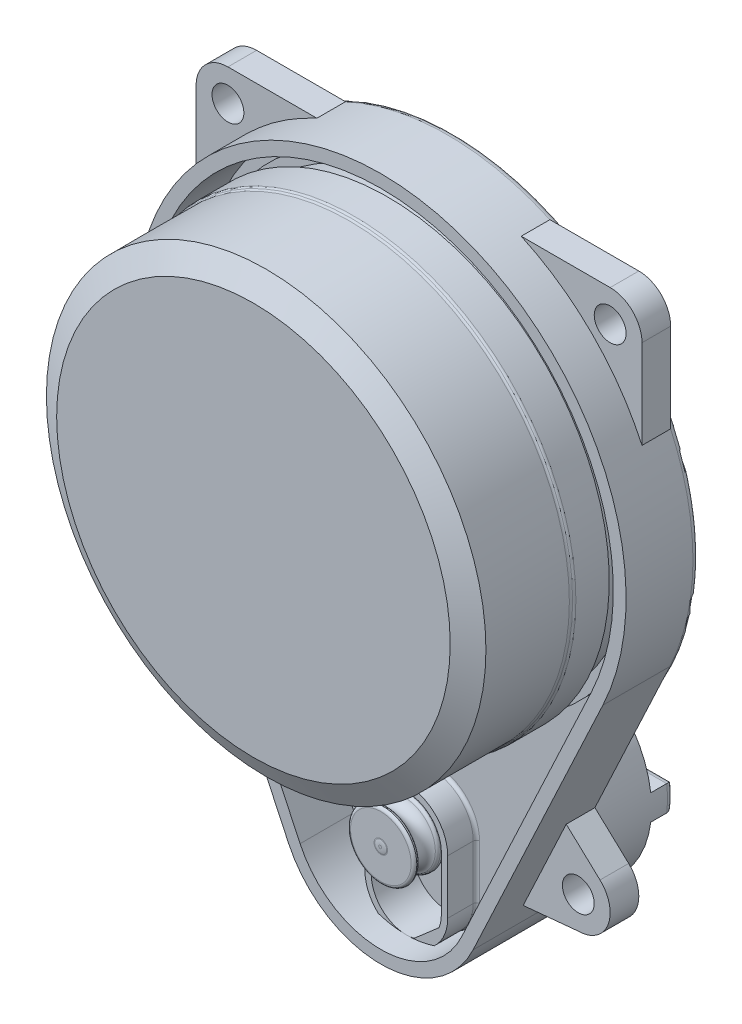
SolidWorks part; units mm, degrees
ref_plane "Front Plane" through (0, 0, 0) normal (0, 0, 1) x (1, 0, 0)
ref_plane "Top Plane" through (0, 0, 0) normal (0, 1, 0) x (1, 0, 0)
ref_plane "Right Plane" through (0, 0, 0) normal (1, 0, 0) x (0, 0, -1)
sketch "Sketch1" plane through (0, 0, 0) normal (0, 0, 1) x (1, 0, 0)
  circle A0 centre (0, 0) radius 34.5
  dimension "D1" = 69
extrude "Boss-Extrude1" add sketch "Sketch1" along normal blind 20
sketch "Sketch3" plane through (0, 0, 0) normal (0, 0, -1) x (-1, 0, 0)
  line L0 (0, 0) -> (0, -53) construction
  line L1 (-14.4866, -59.7925) -> (-34.8585, -16.3443)
  line L2 (14.4866, -59.7925) -> (34.8585, -16.3443)
  line L3 (12.6758, -58.9434) -> (33.0476, -15.4953)
  line L4 (-12.6758, -58.9434) -> (-33.0476, -15.4953)
  arc A2 (34.8585, -16.3443) -> (-34.8585, -16.3443) centre (0, 0) ccw
  circle A3 centre (0, 0) radius 36.5
  circle A4 centre (0, 0) radius 36.5
  arc A6 (-12.6758, -58.9434) -> (12.6758, -58.9434) centre (0, -53) ccw
  circle A7 centre (0, 0) radius 38.5 construction
  arc A8 (-14.4866, -59.7925) -> (14.4866, -59.7925) centre (0, -53) ccw
  point P2 (38.5, 0)
  point P9 (15.3009, -48.3221)
  point P20 (14, -53)
  dimension "D3" = 53
  dimension "D1" = 2
  dimension "D2" = 2
  dimension "D6" = 2
  dimension "D7" = 2
extrude "Boss-Extrude2" add sketch "Sketch3" along normal blind 10.5 separate body contours L1 A8 L2 A2 A6 L4 A4 L3
sketch "Sketch4" plane through (0, 0, 0) normal (0, 0, -1) x (-1, 0, 0)
  circle A2 centre (0, 0) radius 34.5
  circle A3 centre (0, 0) radius 34.5
  dimension "D1" = 0
extrude "Boss-Extrude3" add sketch "Sketch4" along normal blind 10.5
sketch "Sketch5" plane through (0, 0, -10.5) normal (0, 0, -1) x (-1, 0, 0)
  line L4 (-34.8585, -16.3443) -> (-14.4866, -59.7925)
  line L5 (14.4866, -59.7925) -> (34.8585, -16.3443)
  line L6 (-34.8585, -16.3443) -> (-14.4866, -59.7925)
  line L7 (14.4866, -59.7925) -> (34.8585, -16.3443)
  arc A4 (-14.4866, -59.7925) -> (14.4866, -59.7925) centre (0, -53) ccw
  arc A5 (34.8585, -16.3443) -> (-34.8585, -16.3443) centre (0, 0) ccw
  arc A6 (-14.4866, -59.7925) -> (14.4866, -59.7925) centre (0, -53) ccw
  arc A7 (34.8585, -16.3443) -> (-34.8585, -16.3443) centre (0, 0) ccw
  dimension "D1" = 0
extrude "Boss-Extrude4" add sketch "Sketch5" against normal blind 2
sketch "Sketch6" plane through (0, 0, -8.5) normal (0, 0, 1) x (1, 0, 0)
  line L0 (0, -53) -> (0, -61.5) construction
  line L1 (5.5, -53) -> (5.5, -61.5)
  line L2 (-5.5, -53) -> (-5.5, -61.5)
  arc A0 (5.5, -53) -> (-5.5, -53) centre (0, -53) ccw
  arc A1 (-5.5, -61.5) -> (5.5, -61.5) centre (0, -61.5) ccw
  arc A2 (-12.6758, -58.9434) -> (12.6758, -58.9434) centre (0, -53) ccw construction
  point P2 (0, -57.25)
  point P9 (0, -67)
  dimension "D1" = 11
extrude "Cut-Extrude1" cut sketch "Sketch6" against normal blind 2.5
sketch "Sketch7" plane through (0, 0, -10.5) normal (0, 0, -1) x (-1, 0, 0)
  circle A0 centre (0, -53) radius 16
extrude "Boss-Extrude5" add sketch "Sketch7" along normal blind 23
sketch "Sketch8" plane through (0, 0, -33.5) normal (0, 0, -1) x (-1, 0, 0)
  circle A0 centre (0, -53) radius 3.75
  circle A1 centre (0, -53) radius 16
  dimension "D1" = 7.5
extrude "Cut-Extrude2" cut sketch "Sketch8" against normal blind 3.5
sketch "Sketch9" plane through (0, 0, -30) normal (0, 0, -1) x (-1, 0, 0)
  line L0 (3.75, -53) -> (16, -53) construction
  line L1 (0, -49.25) -> (0, -37) construction
  line L2 (2, -49.8279) -> (2, -37.1255)
  line L3 (3.1721, -51) -> (15.8745, -51)
  line L4 (3.75, -51) -> (16, -51) construction
  line L5 (2, -49.25) -> (2, -37) construction
  line L6 (2, -56.1721) -> (2, -68.8745)
  line L7 (3.1721, -55) -> (15.8745, -55)
  line L8 (-3.1721, -55) -> (-15.8745, -55)
  line L9 (-2, -56.1721) -> (-2, -68.8745)
  line L10 (-2, -49.8279) -> (-2, -37.1255)
  line L11 (-3.1721, -51) -> (-15.8745, -51)
  circle A0 centre (0, -53) radius 3.75 construction
  arc A1 (14.4866, -59.7925) -> (-14.4866, -59.7925) centre (0, -53) ccw construction
  circle A2 centre (0, -53) radius 3.75 construction
  circle A3 centre (0, -53) radius 16 construction
  arc A4 (3.1721, -51) -> (2, -49.8279) centre (0, -53) ccw
  arc A5 (2, -56.1721) -> (3.1721, -55) centre (0, -53) ccw
  circle A6 centre (0, -53) radius 16
  arc A7 (15.8745, -51) -> (2, -37.1255) centre (0, -53) ccw
  arc A8 (2, -68.8745) -> (15.8745, -55) centre (0, -53) ccw
  arc A9 (-2, -49.8279) -> (-3.1721, -51) centre (0, -53) ccw
  arc A11 (-15.8745, -55) -> (-2, -68.8745) centre (0, -53) ccw
  arc A12 (-2, -37.1255) -> (-15.8745, -51) centre (0, -53) ccw
  arc A13 (-3.1721, -55) -> (-2, -56.1721) centre (0, -53) ccw
  point P28 (0, -53)
  point P36 (0, -53)
  point P43 (0, -53)
  point P50 (0, -53)
  point P51 (0, -53)
  dimension "D1" = 2
  dimension "D2" = 2
  dimension "D3" = 0
  dimension "D5" = 4
extrude "Cut-Extrude3" cut sketch "Sketch9" against normal blind 3.5
fillet "Fillet1" radius 1 24 edges at (-2, -49.8279, -28.25) (2, -49.8279, -28.25) (2, -56.1721, -28.25) (-2, -56.1721, -28.25) (-3.1721, -55, -28.25) (-3.1721, -51, -28.25) (3.1721, -51, -28.25) (3.1721, -55, -28.25) (0, -37, -30) (-2, -43.4767, -30) (2, -43.4767, -30) (-2, -62.5233, -30) (0, -69, -30) (2, -62.5233, -30) (-9.5233, -51, -30) (-16, -53, -30) (-9.5233, -55, -30) (9.5233, -55, -30) (16, -53, -30) (9.5233, -51, -30) (0, -49.25, -30) (0, -56.75, -30) (-3.75, -53, -30) (3.75, -53, -30)
fillet "Fillet2" radius 1 1 edges at (-3.75, -53, -33.5)
sketch "Sketch10" plane through (0, 0, 0) normal (0, 0, 1) x (1, 0, 0)
  circle A0 centre (0, -53) radius 5.25
  dimension "D1" = 10.5
extrude "Boss-Extrude6" add sketch "Sketch10" against normal blind 4.5 separate body
sketch "Sketch11" plane through (0, 0, -8.5) normal (0, 0, 1) x (1, 0, 0)
  line L2 (-6.5, -53) -> (-6.5, -61.5)
  line L3 (6.5, -61.5) -> (6.5, -53)
  line L4 (-5.5, -53) -> (-5.5, -61.5)
  line L5 (5.5, -61.5) -> (5.5, -53)
  line L6 (-5.5, -53) -> (-5.5, -61.5)
  line L7 (5.5, -61.5) -> (5.5, -53)
  line L8 (4.3894, -66.2941) -> (2.6963, -67.8442)
  line L9 (2.6963, -67.8442) -> (-2.3989, -67.8442)
  line L10 (-2.3989, -67.8442) -> (-4.3894, -66.2941)
  arc A2 (6.5, -53) -> (-6.5, -53) centre (0, -53) ccw
  arc A3 (-6.5, -61.5) -> (-4.3894, -66.2941) centre (0, -61.5) ccw
  arc A4 (5.5, -53) -> (-5.5, -53) centre (0, -53) ccw
  arc A5 (-5.5, -61.5) -> (5.5, -61.5) centre (0, -61.5) ccw
  arc A6 (5.5, -53) -> (-5.5, -53) centre (0, -53) ccw
  arc A7 (-5.5, -61.5) -> (5.5, -61.5) centre (0, -61.5) ccw
  arc A9 (4.3894, -66.2941) -> (6.5, -61.5) centre (0, -61.5) ccw
  arc A13 (-6.5, -61.5) -> (6.5, -61.5) centre (0, -61.5) ccw construction
  dimension "D1" = 0
  dimension "D2" = 1
extrude "Boss-Extrude8" add sketch "Sketch11" along normal blind 4.5
fillet "Fillet3" radius 0.5 5 edges at (5.949, -64.1191, -8.5) (6.5, -57.25, -8.5) (0, -46.5, -8.5) (-5.949, -64.1191, -8.5) (-6.5, -57.25, -8.5)
sketch "Sketch12" plane through (0, 0, 0) normal (0, 0, 1) x (1, 0, 0)
  circle A0 centre (0, -53) radius 1
  dimension "D1" = 2
extrude "Boss-Extrude9" add sketch "Sketch12" against normal blind 14.5 and the other way blind 0.1
fillet "Fillet4" radius 3 1 edges at (1, -53, 0.1)
sketch "Sketch13" plane through (0, 0, 0) normal (1, 0, 0) x (0, 0, -1)
  line L0 (0, -53) -> (4.5, -53) construction
  line L2 (4.5, -54) -> (4.5, -52) construction
  line L3 (4.5, -58.25) -> (4.5, -47.75) construction
  line L4 (0, -53) -> (0, -54) construction
  line L5 (0, -47.75) -> (0, -58.25) construction
  line L6 (0, -52) -> (0, -54) construction
  line L7 (2.25, -53) -> (2.25, -58.4485) construction
  circle A0 centre (2.25, -58.4485) radius 1.4768
  point P4 (4.5, -53)
  point P5 (0, -53)
revolve "Cut-Revolve1" cut sketch "Sketch13" angle 360 about L0
fillet "Fillet5" radius 0.5 2 edges at (-5.25, -53, -0.7866) (5.25, -53, -3.7134)
fillet "Fillet6" radius 0.5 2 edges at (5.25, -53, 0) (1, -53, 0)
chamfer "Chamfer1" distance 2 angle 61 1 edges at (34.5, 0, 20)
sketch "Sketch14" plane through (0, 0, 0) normal (1, 0, 0) x (0, 0, -1)
  line L0 (0, 0) -> (-8.5261, 0) construction
  line L1 (1.0583, -34.7382) -> (6.839, -34.7382)
  line L2 (1.0583, -34.7382) -> (1.0583, -32.6813)
  line L3 (1.0583, -32.6813) -> (6.839, -32.6813)
  line L4 (6.839, -34.7382) -> (6.839, -32.6813)
revolve "Cut-Revolve2" cut sketch "Sketch14" angle 360 about L0
sketch "Sketch15" plane through (0, 0, 0) normal (1, 0, 0) x (0, 0, -1)
  line L0 (1.0583, -34.5) -> (1.0583, 34.5) construction
  line L1 (1.0583, -33.5724) -> (-4.4417, -33.5724)
  line L2 (1.0583, -33.5724) -> (1.0583, -34.8051)
  line L3 (1.0583, -34.8051) -> (-4.4417, -34.8051)
  line L4 (-4.4417, -33.5724) -> (-4.4417, -34.8051)
  line L5 (0, 0) -> (-12.9086, 0) construction
  dimension "D1" = 5.5
revolve "Revolve1" add sketch "Sketch15" angle 360 about L5
fillet "Fillet7" radius 0.5 1 edges at (-34.5, 0, 4.4417)
fillet "Fillet8" radius 0.5 1 edges at (-34.8051, 0, 4.4417)
sketch "Sketch16" plane through (0, 0, 0) normal (1, 0, 0) x (0, 0, -1)
  line L0 (-11.8552, -20.4109) -> (-11.8552, -16.4109) construction
  line L1 (-17.1052, -20.4109) -> (-17.1052, -16.4109)
  line L2 (-6.6052, -20.4109) -> (-6.6052, -16.4109)
  line L3 (-11.8552, -25.6609) -> (-11.8552, -11.1609) construction
  line L4 (-11.8552, 20.6434) -> (-11.8552, 20.1434) construction
  line L5 (-7.8552, 20.6434) -> (-7.8552, 20.1434)
  line L6 (-15.8552, 20.6434) -> (-15.8552, 20.1434)
  line L7 (-11.8552, 16.1434) -> (-11.8552, 24.6434) construction
  arc A0 (-17.1052, -20.4109) -> (-6.6052, -20.4109) centre (-11.8552, -20.4109) ccw
  arc A1 (-6.6052, -16.4109) -> (-17.1052, -16.4109) centre (-11.8552, -16.4109) ccw
  arc A3 (-7.8552, 20.6434) -> (-15.8552, 20.6434) centre (-11.8552, 20.6434) ccw
  arc A4 (-15.8552, 20.1434) -> (-7.8552, 20.1434) centre (-11.8552, 20.1434) ccw
  point P2 (-11.8552, -18.4109)
  point P11 (-11.8552, 20.3934)
  dimension "D3" = 8.5
  dimension "D1" = 14.5
  dimension "D2" = 10.5
  dimension "D4" = 8
extrude "Cut-Extrude4" cut sketch "Sketch16" against normal blind 70.5
sketch "Sketch17" plane through (0, 0, -10.5) normal (0, 0, -1) x (-1, 0, 0)
  line L0 (-25, -50) -> (25, -50) construction
  line L1 (-30, 30) -> (30, 30) construction
  line L2 (0, -50) -> (0, 30) construction
  line L3 (0, -50) -> (0, -69) construction
  line L4 (-30, 35) -> (-13.3287, 35)
  line L5 (-35, 30) -> (-35, 13.9814)
  line L6 (35, 30) -> (35, 13.9814)
  line L7 (35, 13.9814) -> (26.9877, 26.0093)
  line L8 (26.9877, 26.0093) -> (14.4054, 35)
  line L9 (-13.3287, 35) -> (-26.157, 26.8013)
  line L10 (-26.157, 26.8013) -> (-35, 13.9814)
  line L11 (14.4054, 35) -> (30, 35)
  line L12 (25, -55) -> (16.3436, -55.8319)
  line L13 (14.4866, -59.7925) -> (34.8585, -16.3443) construction
  line L14 (28.407, -46.3405) -> (20.8222, -39.279)
  line L15 (20.8222, -39.279) -> (16.3436, -55.8319)
  line L16 (-25, -55) -> (-16.3436, -55.8319)
  line L17 (-28.407, -46.3405) -> (-20.8222, -39.279)
  line L18 (-20.8222, -39.279) -> (-16.3436, -55.8319)
  arc A1 (-14.4866, -59.7925) -> (14.4866, -59.7925) centre (0, -53) ccw construction
  circle A2 centre (0, -53) radius 0.2319 construction
  circle A3 centre (-25, -50) radius 2.5
  circle A4 centre (25, -50) radius 2.5
  circle A5 centre (30, 30) radius 2.5
  circle A6 centre (-30, 30) radius 2.5
  arc A7 (-30, 35) -> (-35, 30) centre (-30, 30) ccw
  arc A8 (35, 30) -> (30, 35) centre (30, 30) ccw
  arc A9 (-28.407, -46.3405) -> (-25, -55) centre (-25, -50) ccw
  arc A10 (25, -55) -> (28.407, -46.3405) centre (25, -50) ccw
  circle A12 centre (-30, 30) radius 5 construction
  circle A13 centre (30, 30) radius 5 construction
  circle A14 centre (-25, -50) radius 5 construction
  circle A15 centre (25, -50) radius 5 construction
  point P17 (35, 30)
  point P21 (30, -50)
  point P34 (-25, 30)
  point P46 (-20, -50)
  line M21 (14.4866, -59.7925) -> (34.8585, -16.3443)
  arc M22 (34.8585, -16.3443) -> (-34.8585, -16.3443) centre (0, 0) ccw
  line M23 (-34.8585, -16.3443) -> (-14.4866, -59.7925)
  dimension "D2" = 5
  dimension "D3" = 5
  dimension "D4" = 5
  dimension "D5" = 5
  dimension "D1" = 3
  dimension "D6" = 2.5
  dimension "D7" = 2.5
  dimension "D8" = 2.5
sketch_block_instance "Block1-1"
sketch_block "Block1"
extrude "Boss-Extrude10" add sketch "Sketch17" against normal blind 4.5 contours L17 A9 L16 A3 M23 | L12 A10 L14 A4 M21 | L6 A8 L11 A5 M22 | L4 A7 L5 A6 M22
sketch "Sketch18" plane through (0, 0, -10.5) normal (0, 0, -1) x (-1, 0, 0)
  circle A0 centre (0, 0) radius 38.5
extrude "Boss-Extrude11" add sketch "Sketch18" along normal blind 1
fillet "Fillet9" radius 1 1 edges at (0, 38.5, -11.5)
sketch "Sketch19" plane through (0, 0, -11.5) normal (0, 0, -1) x (-1, 0, 0)
  circle A0 centre (0, 0) radius 27.5
  arc A1 (3.3349, -37.3514) -> (-3.3349, -37.3514) centre (0, 0) ccw construction
  dimension "D1" = 10
extrude "Boss-Extrude12" add sketch "Sketch19" along normal blind 1
fillet "Fillet10" radius 1 1 edges at (-27.5, 0, -12.5)
sketch "Sketch20" plane through (0, 0, -11.5) normal (0, 0, -1) x (-1, 0, 0)
  line L0 (-49.5406, 38.5) -> (49.5406, 38.5)
  line L1 (49.5406, 38.5) -> (49.5406, -45.4148)
  line L2 (49.5406, -45.4148) -> (28.7514, -66.204)
  line L3 (28.7514, -66.204) -> (16, -66.204)
  line L4 (0, 38.5) -> (0, -72.583) construction
  line L5 (-49.5406, -45.4148) -> (-28.7514, -66.204)
  line L6 (-49.5406, 38.5) -> (-49.5406, -45.4148)
  line L7 (16, -53) -> (16, -66.204)
  line L8 (-16, -53) -> (-16, -66.204)
  line L9 (-16, -66.204) -> (-28.7514, -66.204)
  line L10 (42.5406, 31.5) -> (42.5406, -41.4528) construction
  line L11 (-25, 16.9556) -> (25, 16.9556)
  line L12 (-25, 16.9556) -> (-25, -34.07)
  line L13 (-25, -34.07) -> (25, -34.07)
  line L14 (25, 16.9556) -> (25, -34.07)
  line L15 (-25, 16.9556) -> (25, -34.07) construction
  line L16 (-25, -34.07) -> (25, 16.9556) construction
  arc A0 (16.039, 35) -> (-16.039, 35) centre (0, 0) ccw construction
  circle A1 centre (23, -60.704) radius 1.5
  circle A2 centre (-23, -60.704) radius 1.5
  circle A3 centre (30, 30) radius 2.5
  circle A4 centre (30, 30) radius 2.5
  circle A5 centre (-42.5406, -41.4528) radius 1.5
  circle A6 centre (25, -50) radius 2.5
  circle A7 centre (25, -50) radius 2.5
  circle A8 centre (-42.5406, 31.5) radius 1.5
  circle A9 centre (-30, 30) radius 2.5
  circle A10 centre (-30, 30) radius 2.5
  arc A11 (16, -53) -> (-16, -53) centre (0, -53) ccw
  circle A12 centre (-25, -50) radius 2.5
  circle A13 centre (-25, -50) radius 2.5
  circle A14 centre (42.5406, 31.5) radius 1.5
  circle A15 centre (42.5406, -41.4528) radius 1.5
  arc A16 (15.8745, -51) -> (2, -37.1255) centre (0, -53) ccw construction
  point P13 (0, -8.5572)
  dimension "D5" = 3
  dimension "D6" = 3
  dimension "D7" = 7
  dimension "D8" = 7
  dimension "D9" = 3
  dimension "D10" = 7
  dimension "D11" = 5.5
  dimension "D1" = 0
  dimension "D2" = 0
  dimension "D3" = 0
  dimension "D4" = 0
sketch "Sketch21" plane through (0, 0, -6) normal (0, 0, 1) x (1, 0, 0)
  point P0 (-25, -50)
  point P1 (25, -50)
  point P3 (0, 0)
  point P5 (30, 30)
  point P7 (-30, 30)
